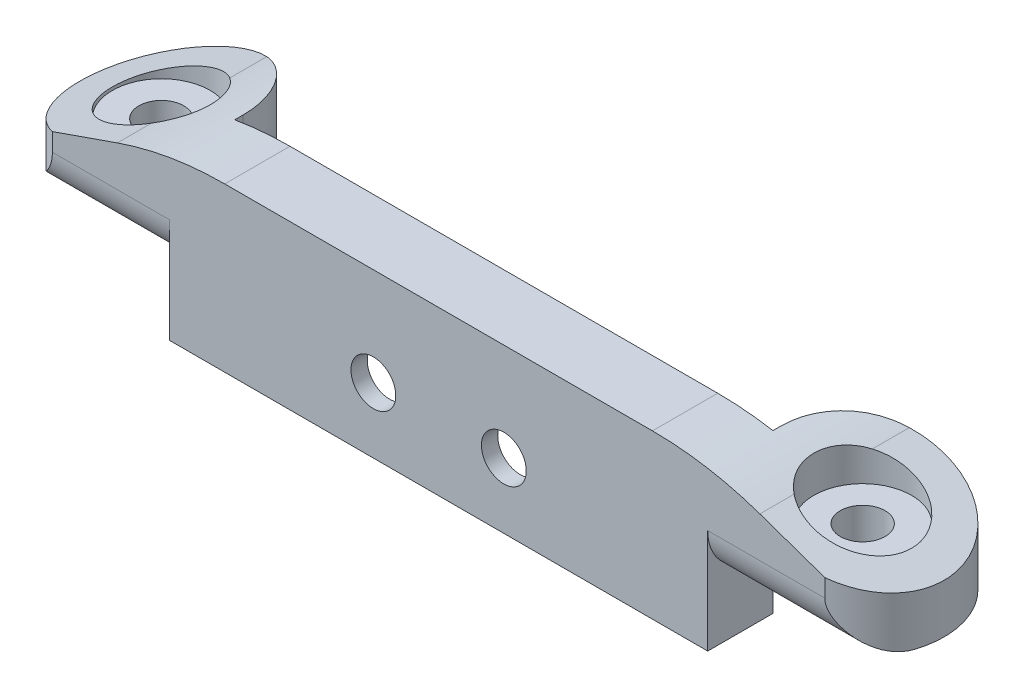
SolidWorks part; units mm, degrees
ref_plane "Front Plane" through (0, 0, 0) normal (0, 0, 1) x (1, 0, 0)
ref_plane "Top Plane" through (0, 0, 0) normal (0, 1, 0) x (1, 0, 0)
ref_plane "Right Plane" through (0, 0, 0) normal (1, 0, 0) x (0, 0, -1)
sketch "Sketch1" plane through (0, 0, 0) normal (0, 0, 1) x (1, 0, 0)
  line L0 (16.5, 0) -> (0, 0) construction
  line L1 (33, 10) -> (0, 10)
  line L2 (33, 10) -> (33, -10)
  line L3 (33, -10) -> (0, -10)
  line L4 (0, 10) -> (0, -10)
  line L5 (33, 10) -> (0, -10) construction
  line L6 (33, -10) -> (0, 10) construction
  point P0 (0, 0)
  point P8 (0, 0)
  point P9 (0, 0)
  dimension "D1" = 33
  dimension "D2" = 20
extrude "Boss-Extrude1" add sketch "Sketch1" along normal mid plane 8
sketch "Sketch2" plane through (0, 10, 0) normal (0, 1, 0) x (1, 0, 0)
  line L0 (33, 5) -> (33, -4)
  line L1 (33, -4) -> (47.3589, -4)
  line L2 (43, 5) -> (43, -4) construction
  arc A0 (47.3589, -4) -> (33, 5) centre (43, 5) ccw
  dimension "D1" = 10
  dimension "D2" = 9
extrude "Boss-Extrude2" add sketch "Sketch2" along normal up to surface from offset 13 up to face at (16.5, 10, 0) offset against normal yes
fillet "Fillet2" radius 5.8 1 edges at (40.1794, -3, 4)
sketch "Sketch3" plane through (0, 10, 0) normal (0, 1, 0) x (1, 0, 0)
  circle A0 centre (43, 5) radius 2.75
  dimension "D1" = 5.5
extrude "Cut-Extrude1" cut sketch "Sketch3" against normal through all both and the other way through all
sketch "Sketch4" plane through (0, 0, 4) normal (0, 0, 1) x (1, 0, 0)
  line L0 (33, 10) -> (53, 3.0241)
  line L1 (53, 3.0241) -> (53, 10)
  line L2 (53, 10) -> (33, 10)
  line L3 (53, -3) -> (53, 10) construction
  point P3 (53, 3.0241)
extrude "Cut-Extrude2" cut sketch "Sketch4" against normal blind 24.26
fillet "Fillet3" radius 40 1 edges at (33, 10, 0) tangent propagation no
sketch "Sketch5" plane through (0, 10, 0) normal (0, 1, 0) x (1, 0, 0)
  circle A0 centre (43, 5) radius 6
  dimension "D1" = 12
extrude "Cut-Extrude3" cut sketch "Sketch5" against normal blind 5.96
mirror "Mirror2" about plane through (0, 10, 4) normal (1, 0, 0) of bodies 106 102
sketch "Sketch7" plane through (0, 0, -4) normal (0, 0, -1) x (-1, 0, 0)
  line L0 (33, -10) -> (-33, -10) construction
  line L1 (-24, 6) -> (24, 6)
  line L2 (-24, 6) -> (-24, -10)
  line L3 (-24, -10) -> (24, -10)
  line L4 (24, 6) -> (24, -10)
  line L5 (-24, 6) -> (24, -10) construction
  line L6 (-24, -10) -> (24, 6) construction
  line L7 (0, 0) -> (0, -2) construction
  point P0 (0, -2)
  dimension "D1" = 48
  dimension "D2" = 16
extrude "Cut-Extrude6" cut sketch "Sketch7" against normal blind 6
fillet "Fillet4" radius 8 2 edges at (-24, 6, -1) (24, 6, -1)
fillet "Fillet5" radius 2 5 edges at (-24, -6, 2) (-21.6569, 3.6569, 2) (0, 6, 2) (21.6569, 3.6569, 2) (24, -6, 2)
sketch "Sketch8" plane through (0, 0, 2) normal (0, 0, -1) x (-1, 0, 0)
  line L0 (-8, -2) -> (8, -2) construction
  line L1 (0, 0) -> (0, -2) construction
  line L2 (-22, -10) -> (22, -10) construction
  circle A0 centre (-8, -2) radius 2.75
  circle A1 centre (8, -2) radius 2.75
  dimension "D1" = 5.5
  dimension "D2" = 16
  dimension "D3" = 8
extrude "Cut-Extrude7" cut sketch "Sketch8" against normal through all both and the other way through all
